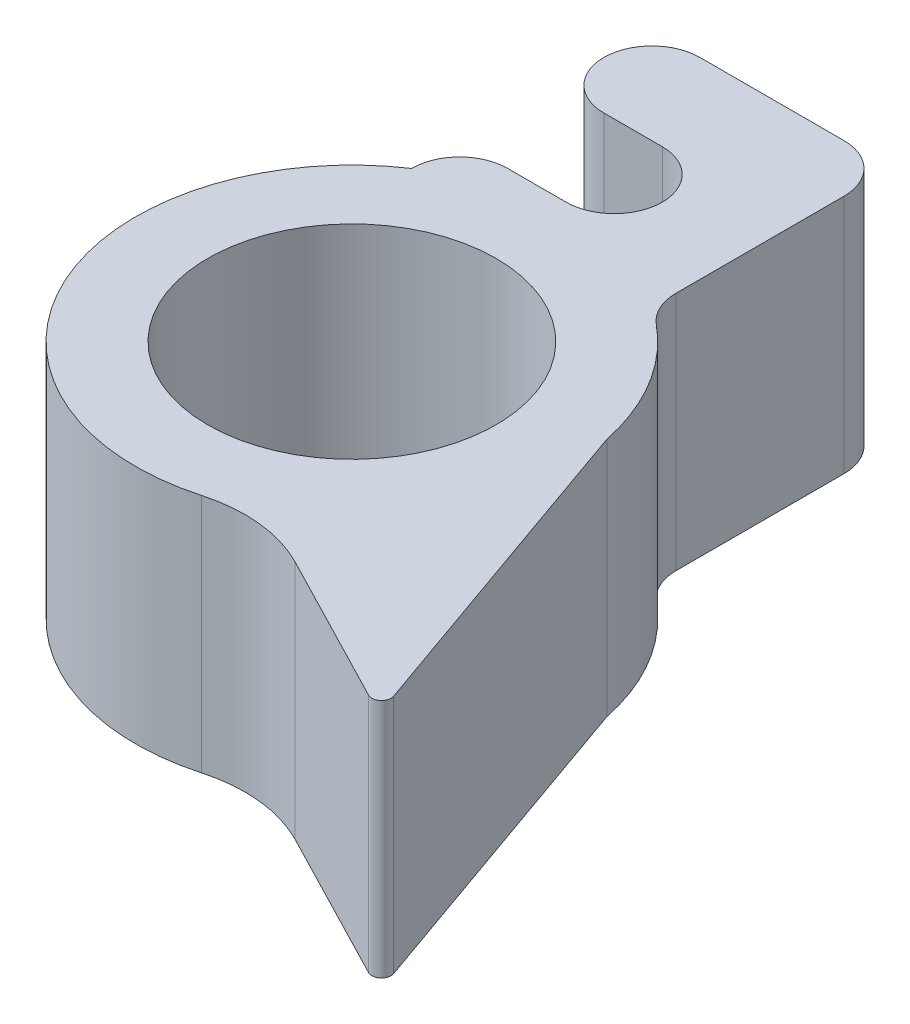
SolidWorks part; units mm, degrees
ref_plane "Front Plane" through (0, 0, 0) normal (0, 0, 1) x (1, 0, 0)
ref_plane "Top Plane" through (0, 0, 0) normal (0, 1, 0) x (1, 0, 0)
ref_plane "Right Plane" through (0, 0, 0) normal (1, 0, 0) x (0, 0, -1)
sketch "Sketch1" plane through (0, 0, 0) normal (0, 1, 0) x (1, 0, 0)
  circle A1 centre (0, 0) radius 5.715
  point P6 (25.8484, 0)
  point P8 (24.5934, 0)
  dimension "D2" = 11.43
extrude "Boss-Extrude1" add sketch "Sketch1" along normal blind 6.35
sketch "Sketch2" plane through (0, 6.35, 0) normal (0, 1, 0) x (1, 0, 0)
  line L3 (5.08, 2.6182) -> (8.8769, -8.1628)
  line L6 (8.8769, -8.1628) -> (2.7646, -5.0018)
  line L7 (5.08, 2.6182) -> (2.7646, -5.0018)
  circle A1 centre (0, 0) radius 5.715 construction
  dimension "D1" = 11.43
  dimension "D3" = 7.62
  dimension "D4" = 5.08
sketch "Sketch3" plane through (0, 6.35, 0) normal (0, 1, 0) x (1, 0, 0)
  circle A0 centre (0, 0) radius 3.81
  point P3 (0, 0)
  dimension "D1" = 7.62
extrude "Cut-Extrude1" cut sketch "Sketch3" against normal blind 6.35
extrude "Boss-Extrude3" add sketch "Sketch2" against normal blind 6.35 contours L3 L6 L7
fillet "Fillet2" radius 0.254 1 edges at (8.8769, 3.175, 8.1628)
fillet "Fillet3" radius 3.81 1 edges at (2.7646, 3.175, 5.0018)
sketch "Sketch4" plane through (0, 6.35, 0) normal (0, 1, 0) x (1, 0, 0)
  line L0 (0, 0) -> (0, 11.3865) construction
  line L1 (-3.175, 4.7519) -> (3.175, 4.7519)
  line L2 (-3.175, 4.7519) -> (-3.175, 11.1019)
  line L3 (-3.175, 11.1019) -> (3.175, 11.1019)
  line L4 (3.175, 4.7519) -> (3.175, 11.1019)
  arc A0 (5.5995, 1.143) -> (1.5278, -5.507) centre (0, 0) ccw construction
  dimension "D1" = 3.175
  dimension "D2" = 3.175
  dimension "D3" = 6.35
extrude "Boss-Extrude4" add sketch "Sketch4" against normal blind 6.35
sketch "Sketch5" plane through (0, 6.35, 0) normal (0, 1, 0) x (1, 0, 0)
  line L0 (-3.175, 11.1019) -> (-3.175, 4.7519) construction
  line L1 (-3.175, 8.5619) -> (0.9104, 8.5619)
  line L2 (-3.175, 8.5619) -> (-3.175, 6.0219)
  line L3 (-3.175, 6.0219) -> (0.9104, 6.0219)
  line L4 (0.9104, 8.5619) -> (0.9104, 6.0219)
  line L5 (3.175, 11.1019) -> (-3.175, 11.1019) construction
  dimension "D1" = 2.54
  dimension "D2" = 2.54
extrude "Cut-Extrude2" cut sketch "Sketch5" against normal blind 6.35
fillet "Fillet4" radius 1.27 7 edges at (3.175, 3.175, -4.7519) (-3.175, 3.175, -6.0219) (0.9104, 3.175, -6.0219) (0.9104, 3.175, -8.5619) (-3.175, 3.175, -8.5619) (-3.175, 3.175, -11.1019) (3.175, 3.175, -11.1019)
